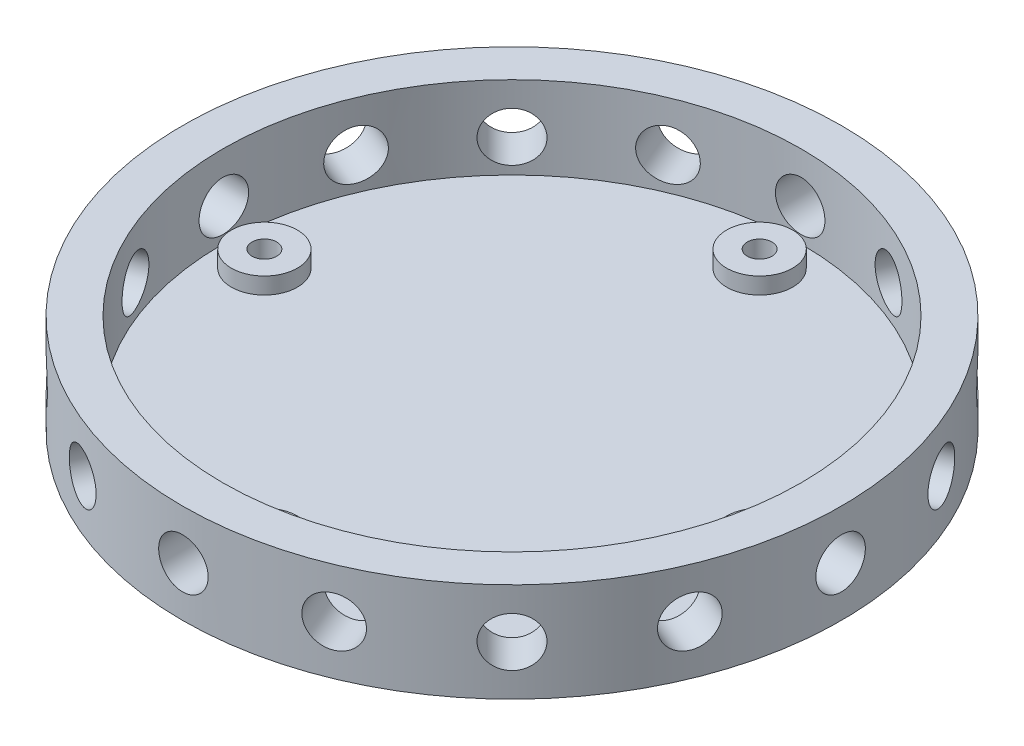
SolidWorks part; units mm, degrees
ref_plane "Front Plane" through (0, 0, 0) normal (0, 0, 1) x (1, 0, 0)
ref_plane "Top Plane" through (0, 0, 0) normal (0, 1, 0) x (1, 0, 0)
ref_plane "Right Plane" through (0, 0, 0) normal (1, 0, 0) x (0, 0, -1)
sketch "Sketch1" plane through (0, 0, 0) normal (0, 1, 0) x (1, 0, 0)
  circle A0 centre (0, 0) radius 63.373
  dimension "D1" = 126.746
extrude "Boss-Extrude1" add sketch "Sketch1" along normal blind 3.175
sketch "Sketch2" plane through (0, 3.175, 0) normal (0, 1, 0) x (1, 0, 0)
  circle A1 centre (0, 0) radius 63.373
  circle A3 centre (0, 0) radius 55.626
  dimension "D1" = 111.252
  dimension "D2" = 126.746
extrude "Boss-Extrude2" add sketch "Sketch2" along normal blind 15.875
sketch "Sketch9" plane through (0, 0, 0) normal (0, 0, 1) x (1, 0, 0)
  line L0 (0, 0) -> (0, 19.05) construction
  line L1 (55.626, 19.05) -> (-55.626, 19.05) construction
  circle A0 centre (0, 9.525) radius 4.7625
  dimension "D1" = 9.525
extrude "Cut-Extrude2" cut sketch "Sketch9" against normal through all
pattern_circular "CirPattern5" count 16 over 360 about axis through (0, 19.05, 0) along (0, -1, 0) of "Cut-Extrude2" reverse direction yes
sketch "Sketch4" plane through (0, 3.175, 0) normal (0, 1, 0) x (1, 0, 0)
  line L0 (0, 0) -> (0, -55.626) construction
  line L1 (0, 0) -> (-55.626, 0) construction
  line L2 (-55.626, 0) -> (-53.975, 0) construction
  line L3 (-53.975, 0) -> (-47.625, 0) construction
  circle A0 centre (0, 0) radius 55.626 construction
  circle A1 centre (0, 0) radius 55.626 construction
  circle A2 centre (-47.625, 0) radius 6.35
  circle A3 centre (-47.625, 0) radius 2.3812
  dimension "D2" = 6.35
  dimension "D3" = 4.7625
  dimension "D1" = 1.651
extrude "Boss-Extrude4" add sketch "Sketch4" along normal blind 3.175
pattern_circular "CirPattern1" count 4 over 360 about axis through (0, 19.05, 0) along (0, 1, 0) of "Boss-Extrude4"
sketch "Sketch8" plane through (0, 19.05, 0) normal (0, 1, 0) x (1, 0, 0)
  circle A0 centre (-57.0304, -0.8343) radius 0.0294
  circle A4 centre (-47.625, 0) radius 2.3812
extrude "Cut-Extrude1" cut sketch "Sketch8" against normal through all
pattern_circular "CirPattern3" count 4 over 360 about axis through (0, 19.05, 0) along (0, 1, 0) of "Cut-Extrude1"
